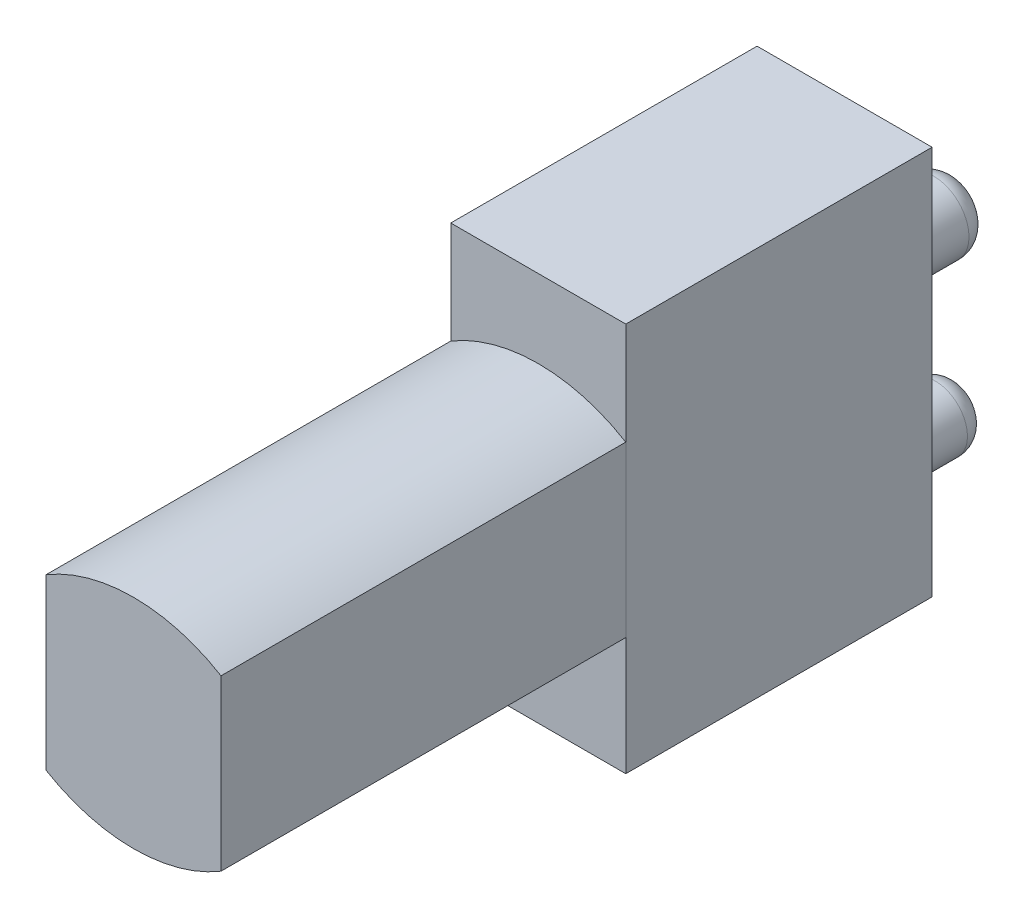
SolidWorks part; units mm, degrees
ref_plane "Front Plane" through (0, 0, 0) normal (0, 0, 1) x (1, 0, 0)
ref_plane "Top Plane" through (0, 0, 0) normal (0, 1, 0) x (1, 0, 0)
ref_plane "Right Plane" through (0, 0, 0) normal (1, 0, 0) x (0, 0, -1)
sketch "Sketch1" plane through (0, 0, 0) normal (0, 0, 1) x (1, 0, 0)
  line L1 (-8.0018, -9.2592) -> (-0.0018, -9.2592)
  line L2 (-8.0018, -9.2592) -> (-8.0018, 8.5408)
  line L3 (-8.0018, 8.5408) -> (-0.0018, 8.5408)
  line L4 (-0.0018, -9.2592) -> (-0.0018, 8.5408)
extrude "Boss-Extrude1" add sketch "Sketch1" along normal blind 14
sketch "Sketch2" plane through (0, 0, 14) normal (0, 0, 1) x (1, 0, 0)
  line L0 (-4.0018, 0) -> (0, 0) construction
  line L1 (-8.0018, -3.8672) -> (-8.0018, 3.8672)
  line L2 (-0.0018, -3.8672) -> (-0.0018, 3.8672)
  arc A0 (-0.0018, -3.8672) -> (-8.0018, -3.8672) centre (-4.0018, 2.7851) cw
  arc A1 (-0.0018, 3.8672) -> (-8.0018, 3.8672) centre (-4.0018, -2.7851) ccw
extrude "Boss-Extrude2" add sketch "Sketch2" along normal blind 18.5 separate body
sketch "Sketch3" plane through (0, 0, 0) normal (0, 0, -1) x (-1, 0, 0)
  line L0 (4.0018, -9.2592) -> (4.0018, -6.2555) construction
  line L1 (8.0018, -9.2592) -> (0.0018, -9.2592) construction
  line L2 (4.0018, -6.2555) -> (4.0018, 1.7473) construction
  circle A0 centre (4.0018, -6.2555) radius 1.4551
  circle A1 centre (4.0018, 1.7473) radius 1.6
  circle A2 centre (4.0018, 1.7473) radius 1.0031
  circle A3 centre (4.0018, -6.2555) radius 0.9973
extrude "Boss-Extrude3" add sketch "Sketch3" along normal blind 5
fillet "Fillet1" radius 1 2 edges at (-5.4569, -6.2555, -5) (-5.6018, 1.7473, -5)
